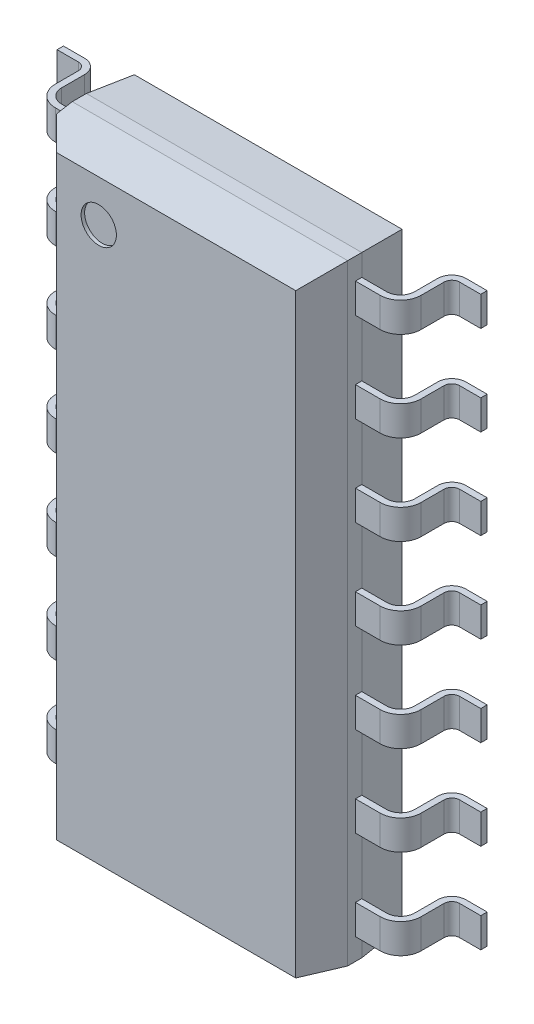
SolidWorks part; units mm, degrees
ref_plane "Face" through (0, 0, 0) normal (0, 0, 1) x (1, 0, 0)
ref_plane "Dessus" through (0, 0, 0) normal (0, 1, 0) x (1, 0, 0)
ref_plane "Droite" through (0, 0, 0) normal (1, 0, 0) x (0, 0, -1)
ref_plane "fond circuit" through (0, 0, 0.1) normal (0, 0, 1) x (1, 0, 0)
sketch "Esquisse2" plane through (0, 0, 0.1) normal (0, 0, 1) x (1, 0, 0)
  line L1 (-1.95, 4.325) -> (1.95, 4.325)
  line L2 (-1.95, 4.325) -> (-1.95, -4.325)
  line L3 (-1.95, -4.325) -> (1.95, -4.325)
  line L4 (1.95, 4.325) -> (1.95, -4.325)
  point P4 (1.95, 0)
  point P6 (0, 4.325)
  dimension "D1" = 3.9
  dimension "D2" = 8.65
extrude "corp" add sketch "Esquisse2" along normal blind 1.45
ref_plane "plan pin 1" through (0, 3.81, 0) normal (0, 1, 0) x (-1, 0, 0)
sketch "Esquisse6" plane through (0, 3.81, 0) normal (0, 1, 0) x (-1, 0, 0)
  line L0 (0, 0) -> (6.8831, 0) construction
  line L1 (1.95, 0.725) -> (2.3, 0.725)
  line L2 (1.95, 1.55) -> (1.95, 0.1) construction
  line L3 (2.5, 0.525) -> (2.5, 0.2)
  line L4 (3, 0) -> (2.7, 0)
  line L6 (-1.95, 1.55) -> (1.95, 1.55) construction
  arc A0 (2.3, 0.725) -> (2.5, 0.525) centre (2.3, 0.525) cw
  arc A1 (2.7, 0) -> (2.5, 0.2) centre (2.7, 0.2) cw
  dimension "D1" = 0.2
  dimension "D2" = 0.5
  dimension "D3" = 1.05
  dimension "D4" = 0.825
extrude "pin 1" add sketch "Esquisse6" along normal mid plane 0.42 thin thin type one direction wall 0.09
pattern_linear "Répétition pin 1-7" count 7 spacing 1.27 along (0, -1, 0) of "pin 1"
mirror "Symétrie1" about plane through (0, 0, 0) normal (1, 0, 0) of "Répétition pin 1-7"
ref_plane "Plan2" through (3.75, 0, 0) normal (1, 0, 0) x (0, 0, -1)
chamfer "Chanfrein4" distance 0.625 angle 10 3 edges at (0, 4.325, 1.55) (1.95, 0, 1.55) (0, -4.325, 1.55) first distance on face at (0, 4.325, 0.825) first distance on face at (1.95, -3.81, 0.77) first distance on face at (0, -4.325, 0.825)
chamfer "Chanfrein5" distance 0.625 angle 5 4 edges at (0, -4.325, 0.1) (1.95, 0, 0.1) (0, 4.325, 0.1) (-1.95, 0, 0.1) first distance on face at (0, -4.325, 0.5125) first distance on face at (1.95, -3.81, 0.77) first distance on face at (0, 4.325, 0.5125) first distance on face at (-1.95, -3.81, 0.77)
sketch "Esquisse8" plane through (0, 0, 1.55) normal (0, 0, 1) x (1, 0, 0)
  line L0 (-1.95, 4.325) -> (-1.95, 4.02) construction
  line L3 (-1.95, 4.325) -> (1.95, 4.325) construction
  circle A0 centre (-0.95, 3.625) radius 0.25
  dimension "D1" = 0.5
  dimension "D2" = 1
  dimension "D3" = 0.7
extrude "Enlèv. mat.-Extru.1" cut sketch "Esquisse8" against normal blind 0.05
chamfer "Chanfrein7" distance 0.4 angle 45 1 edges at (-1.95, 0, 1.55)
